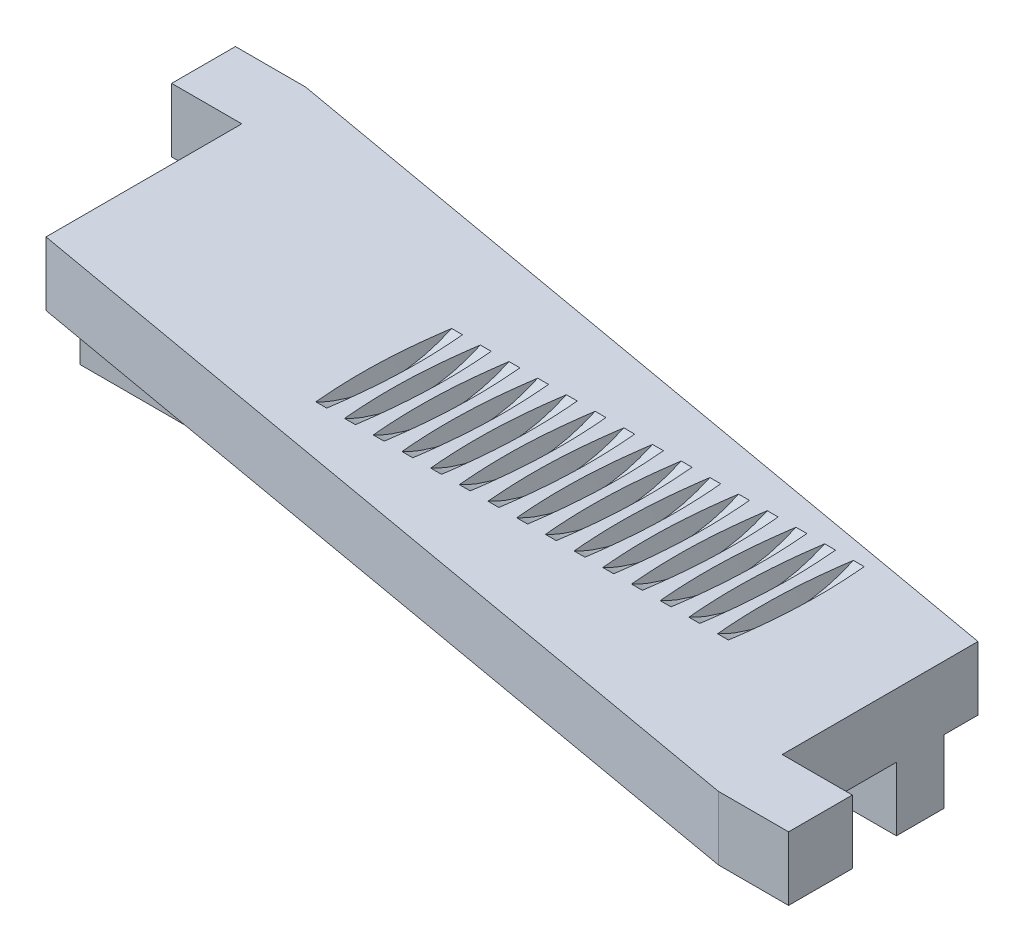
SolidWorks part; units mm, degrees
ref_plane "Front Plane" through (0, 0, 0) normal (0, 0, 1) x (1, 0, 0)
ref_plane "Top Plane" through (0, 0, 0) normal (0, 1, 0) x (1, 0, 0)
ref_plane "Right Plane" through (0, 0, 0) normal (1, 0, 0) x (0, 0, -1)
sketch "Sketch1" plane through (0, 0, 0) normal (0, 1, 0) x (1, 0, 0)
  line L0 (0, 0) -> (-128.025, 22.5743)
  line L1 (0, 40.7057) -> (0, 10)
  line L2 (-128.025, 63.28) -> (0, 40.7057)
  line L3 (0, 10) -> (11, 10)
  line L4 (0, 0) -> (-93.7039, 0) construction
  line L5 (11, 10) -> (11, 0)
  line L6 (11, 0) -> (0, 0)
  line L7 (-128.025, 22.5743) -> (-128.025, 53.28)
  line L8 (-128.025, 53.28) -> (-139.025, 53.28)
  line L9 (-139.025, 53.28) -> (-139.025, 63.28)
  line L10 (-139.025, 63.28) -> (-128.025, 63.28)
  dimension "D1" = 10
  dimension "D2" = 130
  dimension "D3" = 30.7057
  dimension "D4" = 10
  dimension "D5" = 11
  dimension "D6" = 11
extrude "Boss-Extrude1" add sketch "Sketch1" along normal blind 10
sketch "Sketch2" plane through (0, 0, 0) normal (0, -1, 0) x (1, 0, 0)
  line L0 (0, -40.7057) -> (-128.025, -40.7057)
  line L1 (-128.025, -53.28) -> (-128.025, -22.5743) construction
  line L2 (-128.025, -40.7057) -> (-128.025, -22.5743)
  line L3 (-128.025, -22.5743) -> (0, -22.5743)
  line L4 (0, -10) -> (0, -40.7057) construction
  line L5 (0, -22.5743) -> (0, -40.7057)
extrude "Boss-Extrude2" [suppressed] add sketch "Sketch2" along normal blind 10
sketch "Sketch3" plane through (0, 0, 0) normal (1, 0, 0) x (0, 0, -1)
  line L0 (10, 10) -> (10, 0) construction
  line L3 (10, 10) -> (40.7057, 10) construction
  circle A0 centre (31.64, 30) radius 9
  dimension "D1" = 18
  dimension "D2" = 21.64
  dimension "D3" = 20
extrude "Boss-Extrude3" [suppressed] add sketch "Sketch3" against normal blind 200 separate body
sketch "Sketch4" [suppressed] plane through (0, 0, 0) normal (1, 0, 0) x (0, 0, -1)
  line L0 (10, 10) -> (10, 0) construction
  line L1 (10, 10) -> (40.7057, 10) construction
  circle A0 centre (31.64, 19) radius 9
  dimension "D1" = 18
  dimension "D2" = 21.64
  dimension "D3" = 9
ref_plane "Plane1" [suppressed] through (-20, 0, 0) normal (1, 0, 0) x (0, 0, -1)
sketch "Sketch5" [suppressed] plane through (-20, 0, 0) normal (1, 0, 0) x (0, 0, -1)
  circle A0 centre (31.64, 19) radius 9 construction
  circle A1 centre (31.64, 19) radius 9
curve "Helix/Spiral1" [suppressed] pitch 1.5 height 75 turns 50
sketch "Sketch6" [suppressed] plane through (0, 10, 0) normal (0, 1, 0) x (1, 0, 0)
  line L10 (0, 0) -> (11, 0)
  line L11 (11, 0) -> (11, 10)
  line L12 (11, 10) -> (0, 10)
  line L13 (0, 10) -> (0, 40.7057)
  line L14 (0, 40.7057) -> (-128.025, 63.28)
  line L15 (-128.025, 63.28) -> (-139.025, 63.28)
  line L16 (-139.025, 63.28) -> (-139.025, 53.28)
  line L17 (-139.025, 53.28) -> (-128.025, 53.28)
  line L18 (-128.025, 53.28) -> (-128.025, 22.5743)
  line L19 (-128.025, 22.5743) -> (0, 0)
  line L20 (0, 0) -> (11, 0)
  line L21 (11, 0) -> (11, 10)
  line L22 (11, 10) -> (0, 10)
  line L23 (0, 10) -> (0, 40.7057)
  line L24 (0, 40.7057) -> (-128.025, 63.28)
  line L25 (-128.025, 63.28) -> (-139.025, 63.28)
  line L26 (-139.025, 63.28) -> (-139.025, 53.28)
  line L27 (-139.025, 53.28) -> (-128.025, 53.28)
  line L28 (-128.025, 53.28) -> (-128.025, 22.5743)
  line L29 (-128.025, 22.5743) -> (0, 0)
  spline S0 degree 3 poles (-42.5729, 2031.1782) (-14.2433, -98.4369) (-17.5109, 8.3211) (-20.6249, 38.1687) (-20.9375, 40.1716) (-21.25, 40.8742) (-21.5625, 40.1714) (-21.875, 38.1696) (-22.1875, 35.1738) (-22.5, 31.64) (-22.8125, 28.1062) (-23.125, 25.1104) (-23.4375, 23.1086) (-23.75, 22.4057) (-24.0625, 23.1086) (-24.375, 25.1104) (-24.6875, 28.1062) (-25, 31.64) (-25.3125, 35.1738) (-25.625, 38.1696) (-25.9375, 40.1714) (-26.25, 40.8743) (-26.5625, 40.1714) (-26.875, 38.1696) (-27.1875, 35.1738) (-27.5, 31.64) (-27.8125, 28.1062) (-28.125, 25.1104) (-28.4375, 23.1086) (-28.75, 22.4057) (-29.0625, 23.1086) (-29.375, 25.1104) (-29.6875, 28.1062) (-30, 31.64) (-30.3125, 35.1738) (-30.625, 38.1696) (-30.9375, 40.1714) (-31.25, 40.8743) (-31.5625, 40.1714) (-31.875, 38.1696) (-32.1875, 35.1738) (-32.5, 31.64) (-32.8125, 28.1062) (-33.125, 25.1104) (-33.4375, 23.1086) (-33.75, 22.4057) (-34.0625, 23.1086) (-34.375, 25.1104) (-34.6875, 28.1062) (-35, 31.64) (-35.3125, 35.1738) (-35.625, 38.1696) (-35.9375, 40.1714) (-36.25, 40.8743) (-36.5625, 40.1714) (-36.875, 38.1696) (-37.1875, 35.1738) (-37.5, 31.64) (-37.8125, 28.1062) (-38.125, 25.1104) (-38.4375, 23.1086) (-38.75, 22.4057) (-39.0625, 23.1086) (-39.375, 25.1104) (-39.6875, 28.1062) (-40, 31.64) (-40.3125, 35.1738) (-40.625, 38.1696) (-40.9375, 40.1714) (-41.25, 40.8743) (-41.5625, 40.1714) (-41.875, 38.1696) (-42.1875, 35.1738) (-42.5, 31.64) (-42.8125, 28.1062) (-43.125, 25.1104) (-43.4375, 23.1086) (-43.75, 22.4057) (-44.0625, 23.1086) (-44.375, 25.1104) (-44.6875, 28.1062) (-45, 31.64) (-45.3125, 35.1738) (-45.625, 38.1696) (-45.9375, 40.1714) (-46.25, 40.8743) (-46.5625, 40.1714) (-46.875, 38.1696) (-47.1875, 35.1738) (-47.5, 31.64) (-47.8125, 28.1062) (-48.125, 25.1104) (-48.4375, 23.1086) (-48.75, 22.4057) (-49.0625, 23.1086) (-49.375, 25.1104) (-49.6875, 28.1062) (-50, 31.64) (-50.3125, 35.1738) (-50.625, 38.1696) (-50.9375, 40.1714) (-51.25, 40.8743) (-51.5625, 40.1714) (-51.875, 38.1696) (-52.1875, 35.1738) (-52.5, 31.64) (-52.8125, 28.1062) (-53.125, 25.1104) (-53.4375, 23.1086) (-53.75, 22.4057) (-54.0625, 23.1086) (-54.375, 25.1104) (-54.6875, 28.1062) (-55, 31.64) (-55.3125, 35.1738) (-55.625, 38.1696) (-55.9375, 40.1714) (-56.25, 40.8743) (-56.5625, 40.1714) (-56.875, 38.1696) (-57.1875, 35.1738) (-57.5, 31.64) (-57.8125, 28.1062) (-58.125, 25.1104) (-58.4375, 23.1086) (-58.75, 22.4057) (-59.0625, 23.1086) (-59.375, 25.1104) (-59.6875, 28.1062) (-60, 31.64) (-60.3125, 35.1738) (-60.625, 38.1696) (-60.9375, 40.1714) (-61.25, 40.8743) (-61.5625, 40.1714) (-61.875, 38.1696) (-62.1875, 35.1738) (-62.5, 31.64) (-62.8125, 28.1062) (-63.125, 25.1104) (-63.4375, 23.1086) (-63.75, 22.4057) (-64.0625, 23.1086) (-64.375, 25.1104) (-64.6875, 28.1062) (-65, 31.64) (-65.3125, 35.1738) (-65.625, 38.1696) (-65.9375, 40.1714) (-66.25, 40.8743) (-66.5625, 40.1714) (-66.875, 38.1696) (-67.1875, 35.1738) (-67.5, 31.64) (-67.8125, 28.1062) (-68.125, 25.1104) (-68.4375, 23.1086) (-68.75, 22.4057) (-69.0625, 23.1086) (-69.375, 25.1104) (-69.6875, 28.1062) (-70, 31.64) (-70.3125, 35.1738) (-70.625, 38.1696) (-70.9375, 40.1714) (-71.25, 40.8743) (-71.5625, 40.1714) (-71.875, 38.1696) (-72.1875, 35.1738) (-72.5, 31.64) (-72.8125, 28.1062) (-73.125, 25.1104) (-73.4375, 23.1086) (-73.75, 22.4057) (-74.0625, 23.1086) (-74.375, 25.1104) (-74.6875, 28.1062) (-75, 31.64) (-75.3125, 35.1738) (-75.625, 38.1696) (-75.9375, 40.1714) (-76.25, 40.8743) (-76.5625, 40.1714) (-76.875, 38.1696) (-77.1875, 35.1738) (-77.5, 31.64) (-77.8125, 28.1062) (-78.125, 25.1104) (-78.4375, 23.1086) (-78.75, 22.4057) (-79.0625, 23.1086) (-79.375, 25.1104) (-79.6875, 28.1062) (-80, 31.64) (-80.3125, 35.1738) (-80.625, 38.1696) (-80.9375, 40.1714) (-81.25, 40.8743) (-81.5625, 40.1714) (-81.875, 38.1696) (-82.1875, 35.1738) (-82.5, 31.64) (-82.8125, 28.1062) (-83.125, 25.1104) (-83.4375, 23.1086) (-83.75, 22.4057) (-84.0625, 23.1086) (-84.375, 25.1104) (-84.6875, 28.1062) (-85, 31.64) (-85.3125, 35.1738) (-85.625, 38.1696) (-85.9375, 40.1714) (-86.25, 40.8743) (-86.5625, 40.1714) (-86.875, 38.1696) (-87.1875, 35.1738) (-87.5, 31.64) (-87.8125, 28.1062) (-88.125, 25.1104) (-88.4375, 23.1086) (-88.75, 22.4057) (-89.0625, 23.1086) (-89.375, 25.1104) (-89.6875, 28.1062) (-90, 31.64) (-90.3125, 35.1738) (-90.625, 38.1696) (-90.9375, 40.1714) (-91.25, 40.8743) (-91.5625, 40.1714) (-91.875, 38.1696) (-92.1875, 35.1738) (-92.5, 31.64) (-92.8125, 28.1062) (-93.125, 25.1104) (-93.4375, 23.1086) (-93.75, 22.4058) (-94.0625, 23.1084) (-94.3751, 25.1113) (-97.4891, 54.9586) (-100.7566, 161.715) (-72.4279, -1967.8375) knots -0.112218 -0.112218 -0.112218 -0.112218 0.004167 0.008333 0.0125 0.016667 0.020833 0.025 0.029167 0.033333 0.0375 0.041667 0.045833 0.05 0.054167 0.058333 0.0625 0.066667 0.070833 0.075 0.079167 0.083333 0.0875 0.091667 0.095833 0.1 0.104167 0.108333 0.1125 0.116667 0.120833 0.125 0.129167 0.133333 0.1375 0.141667 0.145833 0.15 0.154167 0.158333 0.1625 0.166667 0.170833 0.175 0.179167 0.183333 0.1875 0.191667 0.195833 0.2 0.204167 0.208333 0.2125 0.216667 0.220833 0.225 0.229167 0.233333 0.2375 0.241667 0.245833 0.25 0.254167 0.258333 0.2625 0.266667 0.270833 0.275 0.279167 0.283333 0.2875 0.291667 0.295833 0.3 0.304167 0.308333 0.3125 0.316667 0.320833 0.325 0.329167 0.333333 0.3375 0.341667 0.345833 0.35 0.354167 0.358333 0.3625 0.366667 0.370833 0.375 0.379167 0.383333 0.3875 0.391667 0.395833 0.4 0.404167 0.408333 0.4125 0.416667 0.420833 0.425 0.429167 0.433333 0.4375 0.441667 0.445833 0.45 0.454167 0.458333 0.4625 0.466667 0.470833 0.475 0.479167 0.483333 0.4875 0.491667 0.495833 0.5 0.504167 0.508333 0.5125 0.516667 0.520833 0.525 0.529167 0.533333 0.5375 0.541667 0.545833 0.55 0.554167 0.558333 0.5625 0.566667 0.570833 0.575 0.579167 0.583333 0.5875 0.591667 0.595833 0.6 0.604167 0.608333 0.6125 0.616667 0.620833 0.625 0.629167 0.633333 0.6375 0.641667 0.645833 0.65 0.654167 0.658333 0.6625 0.666667 0.670833 0.675 0.679167 0.683333 0.6875 0.691667 0.695833 0.7 0.704167 0.708333 0.7125 0.716667 0.720833 0.725 0.729167 0.733333 0.7375 0.741667 0.745833 0.75 0.754167 0.758333 0.7625 0.766667 0.770833 0.775 0.779167 0.783333 0.7875 0.791667 0.795833 0.8 0.804167 0.808333 0.8125 0.816667 0.820833 0.825 0.829167 0.833333 0.8375 0.841667 0.845833 0.85 0.854167 0.858333 0.8625 0.866667 0.870833 0.875 0.879167 0.883333 0.8875 0.891667 0.895833 0.9 0.904167 0.908333 0.9125 0.916667 0.920833 0.925 0.929167 0.933333 0.9375 0.941667 0.945833 0.95 0.954167 0.958333 0.9625 0.966667 0.970833 0.975 0.979167 0.983333 0.9875 0.991667 0.995833 1.112217 1.112217 1.112217 1.112217 only from (-20, 31.64) to (-95, 31.64) construction
  spline S1 degree 3 poles (-20, 31.64) (-20.1035, 32.8106) (-20.3128, 35.1772) (-20.6249, 38.1687) (-20.9375, 40.1716) (-21.25, 40.8742) (-21.5625, 40.1714) (-21.875, 38.1696) (-22.1875, 35.1738) (-22.5, 31.64) (-22.8125, 28.1062) (-23.125, 25.1104) (-23.4375, 23.1086) (-23.75, 22.4057) (-24.0625, 23.1086) (-24.375, 25.1104) (-24.6875, 28.1062) (-25, 31.64) (-25.3125, 35.1738) (-25.625, 38.1696) (-25.9375, 40.1714) (-26.25, 40.8743) (-26.5625, 40.1714) (-26.875, 38.1696) (-27.1875, 35.1738) (-27.5, 31.64) (-27.8125, 28.1062) (-28.125, 25.1104) (-28.4375, 23.1086) (-28.75, 22.4057) (-29.0625, 23.1086) (-29.375, 25.1104) (-29.6875, 28.1062) (-30, 31.64) (-30.3125, 35.1738) (-30.625, 38.1696) (-30.9375, 40.1714) (-31.25, 40.8743) (-31.5625, 40.1714) (-31.875, 38.1696) (-32.1875, 35.1738) (-32.5, 31.64) (-32.8125, 28.1062) (-33.125, 25.1104) (-33.4375, 23.1086) (-33.75, 22.4057) (-34.0625, 23.1086) (-34.375, 25.1104) (-34.6875, 28.1062) (-35, 31.64) (-35.3125, 35.1738) (-35.625, 38.1696) (-35.9375, 40.1714) (-36.25, 40.8743) (-36.5625, 40.1714) (-36.875, 38.1696) (-37.1875, 35.1738) (-37.5, 31.64) (-37.8125, 28.1062) (-38.125, 25.1104) (-38.4375, 23.1086) (-38.75, 22.4057) (-39.0625, 23.1086) (-39.375, 25.1104) (-39.6875, 28.1062) (-40, 31.64) (-40.3125, 35.1738) (-40.625, 38.1696) (-40.9375, 40.1714) (-41.25, 40.8743) (-41.5625, 40.1714) (-41.875, 38.1696) (-42.1875, 35.1738) (-42.5, 31.64) (-42.8125, 28.1062) (-43.125, 25.1104) (-43.4375, 23.1086) (-43.75, 22.4057) (-44.0625, 23.1086) (-44.375, 25.1104) (-44.6875, 28.1062) (-45, 31.64) (-45.3125, 35.1738) (-45.625, 38.1696) (-45.9375, 40.1714) (-46.25, 40.8743) (-46.5625, 40.1714) (-46.875, 38.1696) (-47.1875, 35.1738) (-47.5, 31.64) (-47.8125, 28.1062) (-48.125, 25.1104) (-48.4375, 23.1086) (-48.75, 22.4057) (-49.0625, 23.1086) (-49.375, 25.1104) (-49.6875, 28.1062) (-50, 31.64) (-50.3125, 35.1738) (-50.625, 38.1696) (-50.9375, 40.1714) (-51.25, 40.8743) (-51.5625, 40.1714) (-51.875, 38.1696) (-52.1875, 35.1738) (-52.5, 31.64) (-52.8125, 28.1062) (-53.125, 25.1104) (-53.4375, 23.1086) (-53.75, 22.4057) (-54.0625, 23.1086) (-54.375, 25.1104) (-54.6875, 28.1062) (-55, 31.64) (-55.3125, 35.1738) (-55.625, 38.1696) (-55.9375, 40.1714) (-56.25, 40.8743) (-56.5625, 40.1714) (-56.875, 38.1696) (-57.1875, 35.1738) (-57.5, 31.64) (-57.8125, 28.1062) (-58.125, 25.1104) (-58.4375, 23.1086) (-58.75, 22.4057) (-59.0625, 23.1086) (-59.375, 25.1104) (-59.6875, 28.1062) (-60, 31.64) (-60.3125, 35.1738) (-60.625, 38.1696) (-60.9375, 40.1714) (-61.25, 40.8743) (-61.5625, 40.1714) (-61.875, 38.1696) (-62.1875, 35.1738) (-62.5, 31.64) (-62.8125, 28.1062) (-63.125, 25.1104) (-63.4375, 23.1086) (-63.75, 22.4057) (-64.0625, 23.1086) (-64.375, 25.1104) (-64.6875, 28.1062) (-65, 31.64) (-65.3125, 35.1738) (-65.625, 38.1696) (-65.9375, 40.1714) (-66.25, 40.8743) (-66.5625, 40.1714) (-66.875, 38.1696) (-67.1875, 35.1738) (-67.5, 31.64) (-67.8125, 28.1062) (-68.125, 25.1104) (-68.4375, 23.1086) (-68.75, 22.4057) (-69.0625, 23.1086) (-69.375, 25.1104) (-69.6875, 28.1062) (-70, 31.64) (-70.3125, 35.1738) (-70.625, 38.1696) (-70.9375, 40.1714) (-71.25, 40.8743) (-71.5625, 40.1714) (-71.875, 38.1696) (-72.1875, 35.1738) (-72.5, 31.64) (-72.8125, 28.1062) (-73.125, 25.1104) (-73.4375, 23.1086) (-73.75, 22.4057) (-74.0625, 23.1086) (-74.375, 25.1104) (-74.6875, 28.1062) (-75, 31.64) (-75.3125, 35.1738) (-75.625, 38.1696) (-75.9375, 40.1714) (-76.25, 40.8743) (-76.5625, 40.1714) (-76.875, 38.1696) (-77.1875, 35.1738) (-77.5, 31.64) (-77.8125, 28.1062) (-78.125, 25.1104) (-78.4375, 23.1086) (-78.75, 22.4057) (-79.0625, 23.1086) (-79.375, 25.1104) (-79.6875, 28.1062) (-80, 31.64) (-80.3125, 35.1738) (-80.625, 38.1696) (-80.9375, 40.1714) (-81.25, 40.8743) (-81.5625, 40.1714) (-81.875, 38.1696) (-82.1875, 35.1738) (-82.5, 31.64) (-82.8125, 28.1062) (-83.125, 25.1104) (-83.4375, 23.1086) (-83.75, 22.4057) (-84.0625, 23.1086) (-84.375, 25.1104) (-84.6875, 28.1062) (-85, 31.64) (-85.3125, 35.1738) (-85.625, 38.1696) (-85.9375, 40.1714) (-86.25, 40.8743) (-86.5625, 40.1714) (-86.875, 38.1696) (-87.1875, 35.1738) (-87.5, 31.64) (-87.8125, 28.1062) (-88.125, 25.1104) (-88.4375, 23.1086) (-88.75, 22.4057) (-89.0625, 23.1086) (-89.375, 25.1104) (-89.6875, 28.1062) (-90, 31.64) (-90.3125, 35.1738) (-90.625, 38.1696) (-90.9375, 40.1714) (-91.25, 40.8743) (-91.5625, 40.1714) (-91.875, 38.1696) (-92.1875, 35.1738) (-92.5, 31.64) (-92.8125, 28.1062) (-93.125, 25.1104) (-93.4375, 23.1086) (-93.75, 22.4058) (-94.0625, 23.1084) (-94.3751, 25.1113) (-94.6872, 28.1028) (-94.8965, 30.4694) (-95, 31.64) knots 0 0 0 0 0.004167 0.008333 0.0125 0.016667 0.020833 0.025 0.029167 0.033333 0.0375 0.041667 0.045833 0.05 0.054167 0.058333 0.0625 0.066667 0.070833 0.075 0.079167 0.083333 0.0875 0.091667 0.095833 0.1 0.104167 0.108333 0.1125 0.116667 0.120833 0.125 0.129167 0.133333 0.1375 0.141667 0.145833 0.15 0.154167 0.158333 0.1625 0.166667 0.170833 0.175 0.179167 0.183333 0.1875 0.191667 0.195833 0.2 0.204167 0.208333 0.2125 0.216667 0.220833 0.225 0.229167 0.233333 0.2375 0.241667 0.245833 0.25 0.254167 0.258333 0.2625 0.266667 0.270833 0.275 0.279167 0.283333 0.2875 0.291667 0.295833 0.3 0.304167 0.308333 0.3125 0.316667 0.320833 0.325 0.329167 0.333333 0.3375 0.341667 0.345833 0.35 0.354167 0.358333 0.3625 0.366667 0.370833 0.375 0.379167 0.383333 0.3875 0.391667 0.395833 0.4 0.404167 0.408333 0.4125 0.416667 0.420833 0.425 0.429167 0.433333 0.4375 0.441667 0.445833 0.45 0.454167 0.458333 0.4625 0.466667 0.470833 0.475 0.479167 0.483333 0.4875 0.491667 0.495833 0.5 0.504167 0.508333 0.5125 0.516667 0.520833 0.525 0.529167 0.533333 0.5375 0.541667 0.545833 0.55 0.554167 0.558333 0.5625 0.566667 0.570833 0.575 0.579167 0.583333 0.5875 0.591667 0.595833 0.6 0.604167 0.608333 0.6125 0.616667 0.620833 0.625 0.629167 0.633333 0.6375 0.641667 0.645833 0.65 0.654167 0.658333 0.6625 0.666667 0.670833 0.675 0.679167 0.683333 0.6875 0.691667 0.695833 0.7 0.704167 0.708333 0.7125 0.716667 0.720833 0.725 0.729167 0.733333 0.7375 0.741667 0.745833 0.75 0.754167 0.758333 0.7625 0.766667 0.770833 0.775 0.779167 0.783333 0.7875 0.791667 0.795833 0.8 0.804167 0.808333 0.8125 0.816667 0.820833 0.825 0.829167 0.833333 0.8375 0.841667 0.845833 0.85 0.854167 0.858333 0.8625 0.866667 0.870833 0.875 0.879167 0.883333 0.8875 0.891667 0.895833 0.9 0.904167 0.908333 0.9125 0.916667 0.920833 0.925 0.929167 0.933333 0.9375 0.941667 0.945833 0.95 0.954167 0.958333 0.9625 0.966667 0.970833 0.975 0.979167 0.983333 0.9875 0.991667 0.995833 1 1 1 1
  dimension "D1" = 0
sketch "Sketch7" [suppressed] plane through (0, 0, 0) normal (0, 0, 1) x (1, 0, 0)
ref_plane "Plane2" [suppressed] through (0, 0, -31.64) normal (0, 0, 1) x (1, 0, 0)
sketch "Sketch8" [suppressed] plane through (0, 0, -31.64) normal (0, 0, 1) x (1, 0, 0)
  line L0 (-20, 10) -> (-95, 10) construction
  line L1 (0, 10) -> (-128.025, 10) construction
  line L2 (-21, 10) -> (-19, 10)
  arc A0 (-21, 10) -> (-19, 10) centre (-20, 10) ccw
  dimension "D1" = 1
sketch "Sketch9" [suppressed] plane through (0, 0, -31.64) normal (0, 0, 1) x (1, 0, 0)
  circle A0 centre (-20.0422, 27.8584) radius 1
  spline S0 degree 3 poles (-20, 28) (-20.031, 28) (-20.0938, 27.5314) (-20.1875, 25.5296) (-20.2813, 22.5338) (-20.375, 19) (-20.4688, 15.4662) (-20.5625, 12.4704) (-20.6563, 10.4686) (-20.75, 9.7657) (-20.8438, 10.4686) (-20.9375, 12.4704) (-21.0313, 15.4662) (-21.125, 19) (-21.2188, 22.5338) (-21.3125, 25.5296) (-21.4063, 27.5314) (-21.5, 28.2343) (-21.5938, 27.5314) (-21.6875, 25.5296) (-21.7813, 22.5338) (-21.875, 19) (-21.9688, 15.4662) (-22.0625, 12.4704) (-22.1562, 10.4686) (-22.25, 9.7657) (-22.3438, 10.4686) (-22.4375, 12.4704) (-22.5312, 15.4662) (-22.625, 19) (-22.7188, 22.5338) (-22.8125, 25.5296) (-22.9062, 27.5314) (-23, 28.2343) (-23.0938, 27.5314) (-23.1875, 25.5296) (-23.2813, 22.5338) (-23.375, 19) (-23.4688, 15.4662) (-23.5625, 12.4704) (-23.6562, 10.4686) (-23.75, 9.7657) (-23.8438, 10.4686) (-23.9375, 12.4704) (-24.0313, 15.4662) (-24.125, 19) (-24.2188, 22.5338) (-24.3125, 25.5296) (-24.4063, 27.5314) (-24.5, 28.2343) (-24.5938, 27.5314) (-24.6875, 25.5296) (-24.7812, 22.5338) (-24.875, 19) (-24.9688, 15.4662) (-25.0625, 12.4704) (-25.1563, 10.4686) (-25.25, 9.7657) (-25.3438, 10.4686) (-25.4375, 12.4704) (-25.5313, 15.4662) (-25.625, 19) (-25.7188, 22.5338) (-25.8125, 25.5296) (-25.9063, 27.5314) (-26, 28.2343) (-26.0938, 27.5314) (-26.1875, 25.5296) (-26.2813, 22.5338) (-26.375, 19) (-26.4688, 15.4662) (-26.5625, 12.4704) (-26.6563, 10.4686) (-26.75, 9.7657) (-26.8438, 10.4686) (-26.9375, 12.4704) (-27.0313, 15.4662) (-27.125, 19) (-27.2188, 22.5338) (-27.3125, 25.5296) (-27.4063, 27.5314) (-27.5, 28.2343) (-27.5938, 27.5314) (-27.6875, 25.5296) (-27.7813, 22.5338) (-27.875, 19) (-27.9688, 15.4662) (-28.0625, 12.4704) (-28.1563, 10.4686) (-28.25, 9.7657) (-28.3438, 10.4686) (-28.4375, 12.4704) (-28.5313, 15.4662) (-28.625, 19) (-28.7188, 22.5338) (-28.8125, 25.5296) (-28.9063, 27.5314) (-29, 28.2343) (-29.0938, 27.5314) (-29.1875, 25.5296) (-29.2813, 22.5338) (-29.375, 19) (-29.4688, 15.4662) (-29.5625, 12.4704) (-29.6563, 10.4686) (-29.75, 9.7657) (-29.8438, 10.4686) (-29.9375, 12.4704) (-30.0313, 15.4662) (-30.125, 19) (-30.2188, 22.5338) (-30.3125, 25.5296) (-30.4063, 27.5314) (-30.5, 28.2343) (-30.5938, 27.5314) (-30.6875, 25.5296) (-30.7813, 22.5338) (-30.875, 19) (-30.9688, 15.4662) (-31.0625, 12.4704) (-31.1563, 10.4686) (-31.25, 9.7657) (-31.3438, 10.4686) (-31.4375, 12.4704) (-31.5313, 15.4662) (-31.625, 19) (-31.7188, 22.5338) (-31.8125, 25.5296) (-31.9063, 27.5314) (-32, 28.2343) (-32.0938, 27.5314) (-32.1875, 25.5296) (-32.2813, 22.5338) (-32.375, 19) (-32.4688, 15.4662) (-32.5625, 12.4704) (-32.6563, 10.4686) (-32.75, 9.7657) (-32.8438, 10.4686) (-32.9375, 12.4704) (-33.0313, 15.4662) (-33.125, 19) (-33.2188, 22.5338) (-33.3125, 25.5296) (-33.4063, 27.5314) (-33.5, 28.2343) (-33.5938, 27.5314) (-33.6875, 25.5296) (-33.7813, 22.5338) (-33.875, 19) (-33.9688, 15.4662) (-34.0625, 12.4704) (-34.1563, 10.4686) (-34.25, 9.7657) (-34.3438, 10.4686) (-34.4375, 12.4704) (-34.5313, 15.4662) (-34.625, 19) (-34.7188, 22.5338) (-34.8125, 25.5296) (-34.9063, 27.5314) (-35, 28.2343) (-35.0938, 27.5314) (-35.1875, 25.5296) (-35.2813, 22.5338) (-35.375, 19) (-35.4688, 15.4662) (-35.5625, 12.4704) (-35.6563, 10.4686) (-35.75, 9.7657) (-35.8438, 10.4686) (-35.9375, 12.4704) (-36.0313, 15.4662) (-36.125, 19) (-36.2188, 22.5338) (-36.3125, 25.5296) (-36.4063, 27.5314) (-36.5, 28.2343) (-36.5938, 27.5314) (-36.6875, 25.5296) (-36.7813, 22.5338) (-36.875, 19) (-36.9688, 15.4662) (-37.0625, 12.4704) (-37.1563, 10.4686) (-37.25, 9.7657) (-37.3438, 10.4686) (-37.4375, 12.4704) (-37.5313, 15.4662) (-37.625, 19) (-37.7188, 22.5338) (-37.8125, 25.5296) (-37.9063, 27.5314) (-38, 28.2343) (-38.0938, 27.5314) (-38.1875, 25.5296) (-38.2813, 22.5338) (-38.375, 19) (-38.4688, 15.4662) (-38.5625, 12.4704) (-38.6563, 10.4686) (-38.75, 9.7657) (-38.8438, 10.4686) (-38.9375, 12.4704) (-39.0313, 15.4662) (-39.125, 19) (-39.2188, 22.5338) (-39.3125, 25.5296) (-39.4063, 27.5314) (-39.5, 28.2343) (-39.5938, 27.5314) (-39.6875, 25.5296) (-39.7813, 22.5338) (-39.875, 19) (-39.9688, 15.4662) (-40.0625, 12.4704) (-40.1563, 10.4686) (-40.25, 9.7657) (-40.3438, 10.4686) (-40.4375, 12.4704) (-40.5313, 15.4662) (-40.625, 19) (-40.7188, 22.5338) (-40.8125, 25.5296) (-40.9063, 27.5314) (-41, 28.2343) (-41.0938, 27.5314) (-41.1875, 25.5296) (-41.2813, 22.5338) (-41.375, 19) (-41.4688, 15.4662) (-41.5625, 12.4704) (-41.6563, 10.4686) (-41.75, 9.7657) (-41.8438, 10.4686) (-41.9375, 12.4704) (-42.0313, 15.4662) (-42.125, 19) (-42.2188, 22.5338) (-42.3125, 25.5296) (-42.4063, 27.5314) (-42.5, 28.2343) (-42.5938, 27.5314) (-42.6875, 25.5296) (-42.7813, 22.5338) (-42.875, 19) (-42.9688, 15.4662) (-43.0625, 12.4704) (-43.1563, 10.4686) (-43.25, 9.7657) (-43.3438, 10.4686) (-43.4375, 12.4704) (-43.5313, 15.4662) (-43.625, 19) (-43.7188, 22.5338) (-43.8125, 25.5296) (-43.9063, 27.5314) (-44, 28.2343) (-44.0938, 27.5314) (-44.1875, 25.5296) (-44.2813, 22.5338) (-44.375, 19) (-44.4688, 15.4662) (-44.5625, 12.4704) (-44.6563, 10.4686) (-44.75, 9.7657) (-44.8438, 10.4686) (-44.9375, 12.4704) (-45.0313, 15.4662) (-45.125, 19) (-45.2188, 22.5338) (-45.3125, 25.5296) (-45.4063, 27.5314) (-45.5, 28.2343) (-45.5938, 27.5314) (-45.6875, 25.5296) (-45.7813, 22.5338) (-45.875, 19) (-45.9688, 15.4662) (-46.0625, 12.4704) (-46.1563, 10.4686) (-46.25, 9.7657) (-46.3438, 10.4686) (-46.4375, 12.4704) (-46.5313, 15.4662) (-46.625, 19) (-46.7188, 22.5338) (-46.8125, 25.5296) (-46.9063, 27.5314) (-47, 28.2343) (-47.0938, 27.5314) (-47.1875, 25.5296) (-47.2813, 22.5338) (-47.375, 19) (-47.4688, 15.4662) (-47.5625, 12.4704) (-47.6563, 10.4686) (-47.75, 9.7657) (-47.8438, 10.4686) (-47.9375, 12.4704) (-48.0313, 15.4662) (-48.125, 19) (-48.2188, 22.5338) (-48.3125, 25.5296) (-48.4063, 27.5314) (-48.5, 28.2343) (-48.5938, 27.5314) (-48.6875, 25.5296) (-48.7813, 22.5338) (-48.875, 19) (-48.9688, 15.4662) (-49.0625, 12.4704) (-49.1563, 10.4686) (-49.25, 9.7657) (-49.3438, 10.4686) (-49.4375, 12.4704) (-49.5313, 15.4662) (-49.625, 19) (-49.7188, 22.5338) (-49.8125, 25.5296) (-49.9063, 27.5314) (-50, 28.2343) (-50.0938, 27.5314) (-50.1875, 25.5296) (-50.2813, 22.5338) (-50.375, 19) (-50.4688, 15.4662) (-50.5625, 12.4704) (-50.6563, 10.4686) (-50.75, 9.7657) (-50.8438, 10.4686) (-50.9375, 12.4704) (-51.0313, 15.4662) (-51.125, 19) (-51.2188, 22.5338) (-51.3125, 25.5296) (-51.4063, 27.5314) (-51.5, 28.2343) (-51.5938, 27.5314) (-51.6875, 25.5296) (-51.7812, 22.5338) (-51.875, 19) (-51.9687, 15.4662) (-52.0625, 12.4704) (-52.1562, 10.4686) (-52.25, 9.7657) (-52.3437, 10.4686) (-52.4375, 12.4704) (-52.5312, 15.4662) (-52.625, 19) (-52.7187, 22.5338) (-52.8125, 25.5296) (-52.9062, 27.5314) (-53, 28.2343) (-53.0937, 27.5314) (-53.1875, 25.5296) (-53.2812, 22.5338) (-53.375, 19) (-53.4687, 15.4662) (-53.5625, 12.4704) (-53.6562, 10.4686) (-53.75, 9.7657) (-53.8437, 10.4686) (-53.9375, 12.4704) (-54.0312, 15.4662) (-54.125, 19) (-54.2187, 22.5338) (-54.3125, 25.5296) (-54.4062, 27.5314) (-54.5, 28.2343) (-54.5937, 27.5314) (-54.6875, 25.5296) (-54.7812, 22.5338) (-54.875, 19) (-54.9687, 15.4662) (-55.0625, 12.4704) (-55.1562, 10.4686) (-55.25, 9.7657) (-55.3437, 10.4686) (-55.4375, 12.4704) (-55.5312, 15.4662) (-55.625, 19) (-55.7187, 22.5338) (-55.8125, 25.5296) (-55.9062, 27.5314) (-56, 28.2343) (-56.0937, 27.5314) (-56.1875, 25.5296) (-56.2812, 22.5338) (-56.375, 19) (-56.4687, 15.4662) (-56.5625, 12.4704) (-56.6562, 10.4686) (-56.75, 9.7657) (-56.8437, 10.4686) (-56.9375, 12.4704) (-57.0312, 15.4662) (-57.125, 19) (-57.2187, 22.5338) (-57.3125, 25.5296) (-57.4062, 27.5314) (-57.5, 28.2343) (-57.5937, 27.5314) (-57.6875, 25.5296) (-57.7812, 22.5338) (-57.875, 19) (-57.9687, 15.4662) (-58.0625, 12.4704) (-58.1562, 10.4686) (-58.25, 9.7657) (-58.3437, 10.4686) (-58.4375, 12.4704) (-58.5312, 15.4662) (-58.625, 19) (-58.7187, 22.5338) (-58.8125, 25.5296) (-58.9062, 27.5314) (-59, 28.2343) (-59.0937, 27.5314) (-59.1875, 25.5296) (-59.2812, 22.5338) (-59.375, 19) (-59.4687, 15.4662) (-59.5625, 12.4704) (-59.6562, 10.4686) (-59.75, 9.7657) (-59.8437, 10.4686) (-59.9375, 12.4704) (-60.0312, 15.4662) (-60.125, 19) (-60.2187, 22.5338) (-60.3125, 25.5296) (-60.4062, 27.5314) (-60.5, 28.2343) (-60.5937, 27.5314) (-60.6875, 25.5296) (-60.7812, 22.5338) (-60.875, 19) (-60.9687, 15.4662) (-61.0625, 12.4704) (-61.1562, 10.4686) (-61.25, 9.7657) (-61.3437, 10.4686) (-61.4375, 12.4704) (-61.5312, 15.4662) (-61.625, 19) (-61.7187, 22.5338) (-61.8125, 25.5296) (-61.9062, 27.5314) (-62, 28.2343) (-62.0937, 27.5314) (-62.1875, 25.5296) (-62.2812, 22.5338) (-62.375, 19) (-62.4687, 15.4662) (-62.5625, 12.4704) (-62.6562, 10.4686) (-62.75, 9.7657) (-62.8437, 10.4686) (-62.9375, 12.4704) (-63.0312, 15.4662) (-63.125, 19) (-63.2187, 22.5338) (-63.3125, 25.5296) (-63.4062, 27.5314) (-63.5, 28.2343) (-63.5937, 27.5314) (-63.6875, 25.5296) (-63.7812, 22.5338) (-63.875, 19) (-63.9687, 15.4662) (-64.0625, 12.4704) (-64.1562, 10.4686) (-64.25, 9.7657) (-64.3437, 10.4686) (-64.4375, 12.4704) (-64.5312, 15.4662) (-64.625, 19) (-64.7187, 22.5338) (-64.8125, 25.5296) (-64.9062, 27.5314) (-65, 28.2343) (-65.0937, 27.5314) (-65.1875, 25.5296) (-65.2812, 22.5338) (-65.375, 19) (-65.4687, 15.4662) (-65.5625, 12.4704) (-65.6562, 10.4686) (-65.75, 9.7657) (-65.8437, 10.4686) (-65.9375, 12.4704) (-66.0312, 15.4662) (-66.125, 19) (-66.2187, 22.5338) (-66.3125, 25.5296) (-66.4062, 27.5314) (-66.5, 28.2343) (-66.5937, 27.5314) (-66.6875, 25.5296) (-66.7812, 22.5338) (-66.875, 19) (-66.9687, 15.4662) (-67.0625, 12.4704) (-67.1562, 10.4686) (-67.25, 9.7657) (-67.3437, 10.4686) (-67.4375, 12.4704) (-67.5312, 15.4662) (-67.625, 19) (-67.7187, 22.5338) (-67.8125, 25.5296) (-67.9062, 27.5314) (-68, 28.2343) (-68.0937, 27.5314) (-68.1875, 25.5296) (-68.2812, 22.5338) (-68.375, 19) (-68.4687, 15.4662) (-68.5625, 12.4704) (-68.6562, 10.4686) (-68.75, 9.7657) (-68.8437, 10.4686) (-68.9375, 12.4704) (-69.0312, 15.4662) (-69.125, 19) (-69.2187, 22.5338) (-69.3125, 25.5296) (-69.4062, 27.5314) (-69.5, 28.2343) (-69.5937, 27.5314) (-69.6875, 25.5296) (-69.7812, 22.5338) (-69.875, 19) (-69.9687, 15.4662) (-70.0625, 12.4704) (-70.1562, 10.4686) (-70.25, 9.7657) (-70.3437, 10.4686) (-70.4375, 12.4704) (-70.5312, 15.4662) (-70.625, 19) (-70.7187, 22.5338) (-70.8125, 25.5296) (-70.9062, 27.5314) (-71, 28.2343) (-71.0937, 27.5314) (-71.1875, 25.5296) (-71.2812, 22.5338) (-71.375, 19) (-71.4687, 15.4662) (-71.5625, 12.4704) (-71.6562, 10.4686) (-71.75, 9.7657) (-71.8437, 10.4686) (-71.9375, 12.4704) (-72.0312, 15.4662) (-72.125, 19) (-72.2187, 22.5338) (-72.3125, 25.5296) (-72.4062, 27.5314) (-72.5, 28.2343) (-72.5937, 27.5314) (-72.6875, 25.5296) (-72.7812, 22.5338) (-72.875, 19) (-72.9687, 15.4662) (-73.0625, 12.4704) (-73.1562, 10.4686) (-73.25, 9.7657) (-73.3437, 10.4686) (-73.4375, 12.4704) (-73.5312, 15.4662) (-73.625, 19) (-73.7187, 22.5338) (-73.8125, 25.5296) (-73.9062, 27.5314) (-74, 28.2343) (-74.0937, 27.5314) (-74.1875, 25.5296) (-74.2812, 22.5338) (-74.375, 19) (-74.4687, 15.4662) (-74.5625, 12.4704) (-74.6562, 10.4686) (-74.75, 9.7657) (-74.8437, 10.4686) (-74.9375, 12.4704) (-75.0312, 15.4662) (-75.125, 19) (-75.2187, 22.5338) (-75.3125, 25.5296) (-75.4062, 27.5314) (-75.5, 28.2343) (-75.5937, 27.5314) (-75.6875, 25.5296) (-75.7812, 22.5338) (-75.875, 19) (-75.9687, 15.4662) (-76.0625, 12.4704) (-76.1562, 10.4686) (-76.25, 9.7657) (-76.3437, 10.4686) (-76.4375, 12.4704) (-76.5312, 15.4662) (-76.625, 19) (-76.7187, 22.5338) (-76.8125, 25.5296) (-76.9062, 27.5314) (-77, 28.2343) (-77.0937, 27.5314) (-77.1875, 25.5296) (-77.2812, 22.5338) (-77.375, 19) (-77.4687, 15.4662) (-77.5625, 12.4704) (-77.6562, 10.4686) (-77.75, 9.7657) (-77.8437, 10.4686) (-77.9375, 12.4704) (-78.0312, 15.4662) (-78.125, 19) (-78.2187, 22.5338) (-78.3125, 25.5296) (-78.4062, 27.5314) (-78.5, 28.2343) (-78.5937, 27.5314) (-78.6875, 25.5296) (-78.7812, 22.5338) (-78.875, 19) (-78.9687, 15.4662) (-79.0625, 12.4704) (-79.1562, 10.4686) (-79.25, 9.7657) (-79.3437, 10.4686) (-79.4375, 12.4704) (-79.5312, 15.4662) (-79.625, 19) (-79.7187, 22.5338) (-79.8125, 25.5296) (-79.9062, 27.5314) (-80, 28.2343) (-80.0937, 27.5314) (-80.1875, 25.5296) (-80.2812, 22.5338) (-80.375, 19) (-80.4687, 15.4662) (-80.5625, 12.4704) (-80.6562, 10.4686) (-80.75, 9.7657) (-80.8437, 10.4686) (-80.9375, 12.4704) (-81.0312, 15.4662) (-81.125, 19) (-81.2187, 22.5338) (-81.3125, 25.5296) (-81.4062, 27.5314) (-81.5, 28.2343) (-81.5937, 27.5314) (-81.6875, 25.5296) (-81.7812, 22.5338) (-81.875, 19) (-81.9687, 15.4662) (-82.0625, 12.4704) (-82.1562, 10.4686) (-82.25, 9.7657) (-82.3437, 10.4686) (-82.4375, 12.4704) (-82.5312, 15.4662) (-82.625, 19) (-82.7187, 22.5338) (-82.8125, 25.5296) (-82.9062, 27.5314) (-83, 28.2343) (-83.0937, 27.5314) (-83.1875, 25.5296) (-83.2812, 22.5338) (-83.375, 19) (-83.4687, 15.4662) (-83.5625, 12.4704) (-83.6562, 10.4686) (-83.75, 9.7657) (-83.8437, 10.4686) (-83.9375, 12.4704) (-84.0312, 15.4662) (-84.125, 19) (-84.2187, 22.5338) (-84.3125, 25.5296) (-84.4062, 27.5314) (-84.5, 28.2343) (-84.5937, 27.5314) (-84.6875, 25.5296) (-84.7812, 22.5338) (-84.875, 19) (-84.9687, 15.4662) (-85.0625, 12.4704) (-85.1562, 10.4686) (-85.25, 9.7657) (-85.3437, 10.4686) (-85.4375, 12.4704) (-85.5312, 15.4662) (-85.625, 19) (-85.7187, 22.5338) (-85.8125, 25.5296) (-85.9062, 27.5314) (-86, 28.2343) (-86.0937, 27.5314) (-86.1875, 25.5296) (-86.2812, 22.5338) (-86.375, 19) (-86.4687, 15.4662) (-86.5625, 12.4704) (-86.6562, 10.4686) (-86.75, 9.7657) (-86.8437, 10.4686) (-86.9375, 12.4704) (-87.0312, 15.4662) (-87.125, 19) (-87.2187, 22.5338) (-87.3125, 25.5296) (-87.4062, 27.5314) (-87.5, 28.2343) (-87.5937, 27.5314) (-87.6875, 25.5296) (-87.7812, 22.5338) (-87.875, 19) (-87.9687, 15.4662) (-88.0625, 12.4704) (-88.1562, 10.4686) (-88.25, 9.7657) (-88.3437, 10.4686) (-88.4375, 12.4704) (-88.5312, 15.4662) (-88.625, 19) (-88.7187, 22.5338) (-88.8125, 25.5296) (-88.9062, 27.5314) (-89, 28.2343) (-89.0937, 27.5314) (-89.1875, 25.5296) (-89.2812, 22.5338) (-89.375, 19) (-89.4687, 15.4662) (-89.5625, 12.4704) (-89.6562, 10.4686) (-89.75, 9.7657) (-89.8437, 10.4686) (-89.9375, 12.4704) (-90.0312, 15.4662) (-90.125, 19) (-90.2187, 22.5338) (-90.3125, 25.5296) (-90.4062, 27.5314) (-90.5, 28.2343) (-90.5937, 27.5314) (-90.6875, 25.5296) (-90.7812, 22.5338) (-90.875, 19) (-90.9687, 15.4662) (-91.0625, 12.4704) (-91.1562, 10.4686) (-91.25, 9.7657) (-91.3437, 10.4686) (-91.4375, 12.4704) (-91.5312, 15.4662) (-91.625, 19) (-91.7187, 22.5338) (-91.8125, 25.5296) (-91.9062, 27.5314) (-92, 28.2343) (-92.0937, 27.5314) (-92.1875, 25.5296) (-92.2812, 22.5338) (-92.375, 19) (-92.4687, 15.4662) (-92.5625, 12.4704) (-92.6562, 10.4686) (-92.75, 9.7657) (-92.8437, 10.4686) (-92.9375, 12.4704) (-93.0312, 15.4662) (-93.125, 19) (-93.2187, 22.5338) (-93.3125, 25.5296) (-93.4062, 27.5314) (-93.5, 28.2343) (-93.5937, 27.5314) (-93.6875, 25.5296) (-93.7812, 22.5338) (-93.875, 19) (-93.9687, 15.4662) (-94.0625, 12.4704) (-94.1562, 10.4686) (-94.25, 9.7657) (-94.3437, 10.4686) (-94.4375, 12.4704) (-94.5312, 15.4662) (-94.625, 19) (-94.7187, 22.5338) (-94.8125, 25.5296) (-94.9062, 27.5314) (-94.969, 28) (-95, 28) knots 0 0 0 0 0.00125 0.0025 0.00375 0.005 0.00625 0.0075 0.00875 0.01 0.01125 0.0125 0.01375 0.015 0.01625 0.0175 0.01875 0.02 0.02125 0.0225 0.02375 0.025 0.02625 0.0275 0.02875 0.03 0.03125 0.0325 0.03375 0.035 0.03625 0.0375 0.03875 0.04 0.04125 0.0425 0.04375 0.045 0.04625 0.0475 0.04875 0.05 0.05125 0.0525 0.05375 0.055 0.05625 0.0575 0.05875 0.06 0.06125 0.0625 0.06375 0.065 0.06625 0.0675 0.06875 0.07 0.07125 0.0725 0.07375 0.075 0.07625 0.0775 0.07875 0.08 0.08125 0.0825 0.08375 0.085 0.08625 0.0875 0.08875 0.09 0.09125 0.0925 0.09375 0.095 0.09625 0.0975 0.09875 0.1 0.10125 0.1025 0.10375 0.105 0.10625 0.1075 0.10875 0.11 0.11125 0.1125 0.11375 0.115 0.11625 0.1175 0.11875 0.12 0.12125 0.1225 0.12375 0.125 0.12625 0.1275 0.12875 0.13 0.13125 0.1325 0.13375 0.135 0.13625 0.1375 0.13875 0.14 0.14125 0.1425 0.14375 0.145 0.14625 0.1475 0.14875 0.15 0.15125 0.1525 0.15375 0.155 0.15625 0.1575 0.15875 0.16 0.16125 0.1625 0.16375 0.165 0.16625 0.1675 0.16875 0.17 0.17125 0.1725 0.17375 0.175 0.17625 0.1775 0.17875 0.18 0.18125 0.1825 0.18375 0.185 0.18625 0.1875 0.18875 0.19 0.19125 0.1925 0.19375 0.195 0.19625 0.1975 0.19875 0.2 0.20125 0.2025 0.20375 0.205 0.20625 0.2075 0.20875 0.21 0.21125 0.2125 0.21375 0.215 0.21625 0.2175 0.21875 0.22 0.22125 0.2225 0.22375 0.225 0.22625 0.2275 0.22875 0.23 0.23125 0.2325 0.23375 0.235 0.23625 0.2375 0.23875 0.24 0.24125 0.2425 0.24375 0.245 0.24625 0.2475 0.24875 0.25 0.25125 0.2525 0.25375 0.255 0.25625 0.2575 0.25875 0.26 0.26125 0.2625 0.26375 0.265 0.26625 0.2675 0.26875 0.27 0.27125 0.2725 0.27375 0.275 0.27625 0.2775 0.27875 0.28 0.28125 0.2825 0.28375 0.285 0.28625 0.2875 0.28875 0.29 0.29125 0.2925 0.29375 0.295 0.29625 0.2975 0.29875 0.3 0.30125 0.3025 0.30375 0.305 0.30625 0.3075 0.30875 0.31 0.31125 0.3125 0.31375 0.315 0.31625 0.3175 0.31875 0.32 0.32125 0.3225 0.32375 0.325 0.32625 0.3275 0.32875 0.33 0.33125 0.3325 0.33375 0.335 0.33625 0.3375 0.33875 0.34 0.34125 0.3425 0.34375 0.345 0.34625 0.3475 0.34875 0.35 0.35125 0.3525 0.35375 0.355 0.35625 0.3575 0.35875 0.36 0.36125 0.3625 0.36375 0.365 0.36625 0.3675 0.36875 0.37 0.37125 0.3725 0.37375 0.375 0.37625 0.3775 0.37875 0.38 0.38125 0.3825 0.38375 0.385 0.38625 0.3875 0.38875 0.39 0.39125 0.3925 0.39375 0.395 0.39625 0.3975 0.39875 0.4 0.40125 0.4025 0.40375 0.405 0.40625 0.4075 0.40875 0.41 0.41125 0.4125 0.41375 0.415 0.41625 0.4175 0.41875 0.42 0.42125 0.4225 0.42375 0.425 0.42625 0.4275 0.42875 0.43 0.43125 0.4325 0.43375 0.435 0.43625 0.4375 0.43875 0.44 0.44125 0.4425 0.44375 0.445 0.44625 0.4475 0.44875 0.45 0.45125 0.4525 0.45375 0.455 0.45625 0.4575 0.45875 0.46 0.46125 0.4625 0.46375 0.465 0.46625 0.4675 0.46875 0.47 0.47125 0.4725 0.47375 0.475 0.47625 0.4775 0.47875 0.48 0.48125 0.4825 0.48375 0.485 0.48625 0.4875 0.48875 0.49 0.49125 0.4925 0.49375 0.495 0.49625 0.4975 0.49875 0.5 0.50125 0.5025 0.50375 0.505 0.50625 0.5075 0.50875 0.51 0.51125 0.5125 0.51375 0.515 0.51625 0.5175 0.51875 0.52 0.52125 0.5225 0.52375 0.525 0.52625 0.5275 0.52875 0.53 0.53125 0.5325 0.53375 0.535 0.53625 0.5375 0.53875 0.54 0.54125 0.5425 0.54375 0.545 0.54625 0.5475 0.54875 0.55 0.55125 0.5525 0.55375 0.555 0.55625 0.5575 0.55875 0.56 0.56125 0.5625 0.56375 0.565 0.56625 0.5675 0.56875 0.57 0.57125 0.5725 0.57375 0.575 0.57625 0.5775 0.57875 0.58 0.58125 0.5825 0.58375 0.585 0.58625 0.5875 0.58875 0.59 0.59125 0.5925 0.59375 0.595 0.59625 0.5975 0.59875 0.6 0.60125 0.6025 0.60375 0.605 0.60625 0.6075 0.60875 0.61 0.61125 0.6125 0.61375 0.615 0.61625 0.6175 0.61875 0.62 0.62125 0.6225 0.62375 0.625 0.62625 0.6275 0.62875 0.63 0.63125 0.6325 0.63375 0.635 0.63625 0.6375 0.63875 0.64 0.64125 0.6425 0.64375 0.645 0.64625 0.6475 0.64875 0.65 0.65125 0.6525 0.65375 0.655 0.65625 0.6575 0.65875 0.66 0.66125 0.6625 0.66375 0.665 0.66625 0.6675 0.66875 0.67 0.67125 0.6725 0.67375 0.675 0.67625 0.6775 0.67875 0.68 0.68125 0.6825 0.68375 0.685 0.68625 0.6875 0.68875 0.69 0.69125 0.6925 0.69375 0.695 0.69625 0.6975 0.69875 0.7 0.70125 0.7025 0.70375 0.705 0.70625 0.7075 0.70875 0.71 0.71125 0.7125 0.71375 0.715 0.71625 0.7175 0.71875 0.72 0.72125 0.7225 0.72375 0.725 0.72625 0.7275 0.72875 0.73 0.73125 0.7325 0.73375 0.735 0.73625 0.7375 0.73875 0.74 0.74125 0.7425 0.74375 0.745 0.74625 0.7475 0.74875 0.75 0.75125 0.7525 0.75375 0.755 0.75625 0.7575 0.75875 0.76 0.76125 0.7625 0.76375 0.765 0.76625 0.7675 0.76875 0.77 0.77125 0.7725 0.77375 0.775 0.77625 0.7775 0.77875 0.78 0.78125 0.7825 0.78375 0.785 0.78625 0.7875 0.78875 0.79 0.79125 0.7925 0.79375 0.795 0.79625 0.7975 0.79875 0.8 0.80125 0.8025 0.80375 0.805 0.80625 0.8075 0.80875 0.81 0.81125 0.8125 0.81375 0.815 0.81625 0.8175 0.81875 0.82 0.82125 0.8225 0.82375 0.825 0.82625 0.8275 0.82875 0.83 0.83125 0.8325 0.83375 0.835 0.83625 0.8375 0.83875 0.84 0.84125 0.8425 0.84375 0.845 0.84625 0.8475 0.84875 0.85 0.85125 0.8525 0.85375 0.855 0.85625 0.8575 0.85875 0.86 0.86125 0.8625 0.86375 0.865 0.86625 0.8675 0.86875 0.87 0.87125 0.8725 0.87375 0.875 0.87625 0.8775 0.87875 0.88 0.88125 0.8825 0.88375 0.885 0.88625 0.8875 0.88875 0.89 0.89125 0.8925 0.89375 0.895 0.89625 0.8975 0.89875 0.9 0.90125 0.9025 0.90375 0.905 0.90625 0.9075 0.90875 0.91 0.91125 0.9125 0.91375 0.915 0.91625 0.9175 0.91875 0.92 0.92125 0.9225 0.92375 0.925 0.92625 0.9275 0.92875 0.93 0.93125 0.9325 0.93375 0.935 0.93625 0.9375 0.93875 0.94 0.94125 0.9425 0.94375 0.945 0.94625 0.9475 0.94875 0.95 0.95125 0.9525 0.95375 0.955 0.95625 0.9575 0.95875 0.96 0.96125 0.9625 0.96375 0.965 0.96625 0.9675 0.96875 0.97 0.97125 0.9725 0.97375 0.975 0.97625 0.9775 0.97875 0.98 0.98125 0.9825 0.98375 0.985 0.98625 0.9875 0.98875 0.99 0.99125 0.9925 0.99375 0.995 0.99625 0.9975 0.99875 1 1 1 1 construction
  dimension "D1" = 2
sweep "Cut-Sweep1" [suppressed] cut profiles "Sketch9" path "Helix/Spiral1"
ref_plane "Plane3" through (-20, 0, 0) normal (1, 0, 0) x (0, 0, -1)
sketch "Sketch11" plane through (-20, 0, 0) normal (1, 0, 0) x (0, 0, -1)
  line L0 (10, 10) -> (10, 0) construction
  line L1 (10, 10) -> (40.7057, 10) construction
  circle A0 centre (31.64, 30) radius 22.5
  dimension "D1" = 45
  dimension "D2" = 21.64
  dimension "D3" = 20
curve "Helix/Spiral2" pitch 4.5 height 64.5 radius 22.5 centre (-20, 30, -31.64) axis (-1, 0, 0) start towards (0, 0, -1)
ref_plane "Plane4" through (0, 30, 0) normal (0, 1, 0) x (1, 0, 0)
sketch "Sketch12" plane through (0, 30, 0) normal (0, 1, 0) x (1, 0, 0)
  line L0 (-20.6983, 51.44) -> (-17.6017, 51.44)
  line L4 (-19.15, 48.6659) -> (-19.15, 53.291) construction
  line L11 (-20, 54.14) -> (-20.6983, 51.44)
  line L12 (-17.6017, 51.44) -> (-18.3, 54.14)
  line L13 (-18.3, 54.14) -> (-20, 54.14)
  dimension "D1" = 1.7
  dimension "D2" = 2.7
  dimension "D3" = 29
sweep "Cut-Sweep2" cut profiles "Sketch12" path "Helix/Spiral2" align with end faces yes
sketch "Sketch13" plane through (0, 0, 0) normal (0, -1, 0) x (1, 0, 0)
  line L0 (0, -35.4057) -> (-128.025, -35.4057)
  line L1 (0, -10) -> (0, -40.7057) construction
  line L2 (-128.025, -53.28) -> (-128.025, -22.5743) construction
  line L3 (-128.025, -35.4057) -> (-128.025, -27.9057)
  line L4 (-128.025, -27.9057) -> (0, -27.9057)
  line L5 (0, -27.9057) -> (0, -35.4057)
  dimension "D1" = 5.3
  dimension "D2" = 7.5
extrude "Boss-Extrude4" add sketch "Sketch13" along normal blind 10
